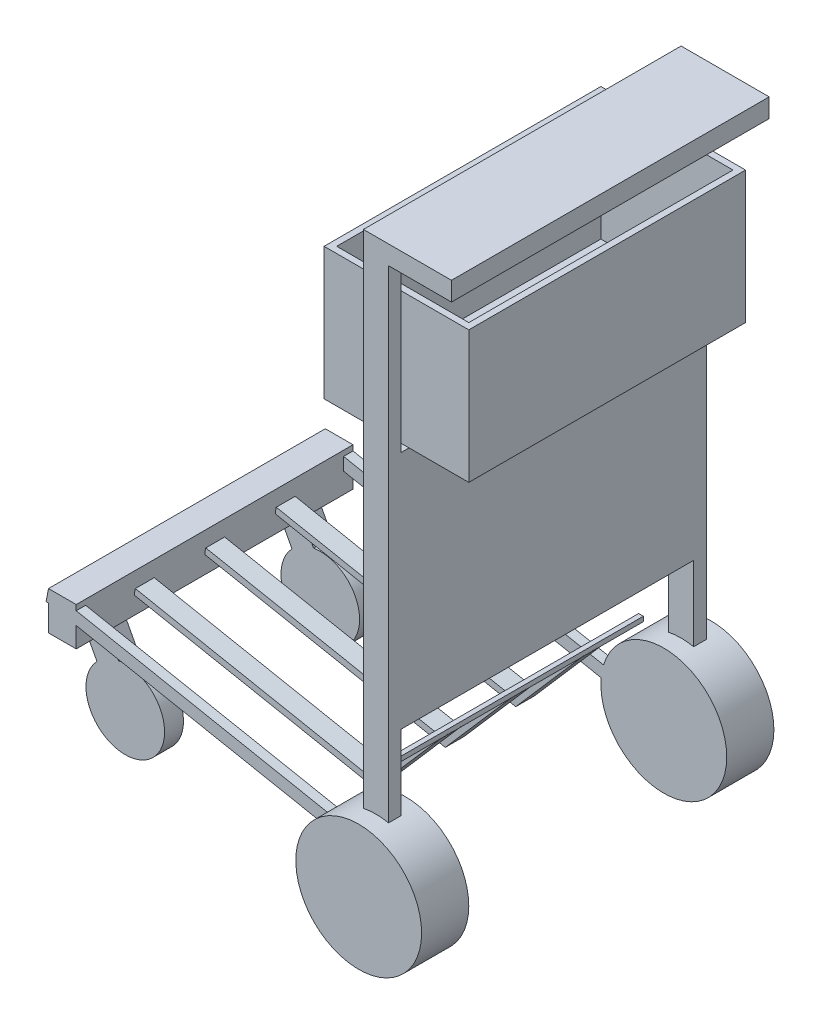
SolidWorks part; units mm, degrees
ref_plane "Front Plane" through (0, 0, 0) normal (0, 0, 1) x (1, 0, 0)
ref_plane "Top Plane" through (0, 0, 0) normal (0, 1, 0) x (1, 0, 0)
ref_plane "Right Plane" through (0, 0, 0) normal (1, 0, 0) x (0, 0, -1)
sketch "Sketch1" plane through (0, 0, 0) normal (1, 0, 0) x (0, 0, -1)
  line L0 (0, 0) -> (0, 459.3185) construction
  line L10 (-232.5, 0) -> (-252.5, 0)
  line L11 (-232.5, 0) -> (-232.5, 965)
  line L13 (-252.5, 0) -> (-252.5, 995)
  line L14 (252.5, 0) -> (252.5, 995)
  line L15 (232.5, 0) -> (252.5, 0)
  line L16 (232.5, 0) -> (232.5, 965)
  line L18 (-252.5, 995) -> (252.5, 995)
  line L20 (-232.5, 965) -> (232.5, 965)
  dimension "D2" = 465
  dimension "D3" = 995
  dimension "D4" = 30
  dimension "D5" = 20
extrude "Boss-Extrude1" add sketch "Sketch1" along normal blind 40
sketch "Sketch3" plane through (40, 0, 0) normal (1, 0, 0) x (0, 0, -1)
  line L0 (252.5, 0) -> (252.5, 995) construction
  line L1 (-252.5, 995) -> (252.5, 995)
  line L2 (-252.5, 995) -> (-252.5, 965)
  line L3 (-252.5, 965) -> (252.5, 965)
  line L4 (252.5, 995) -> (252.5, 965)
  line L5 (-232.5, 965) -> (232.5, 965) construction
extrude "Boss-Extrude2" add sketch "Sketch3" along normal blind 100
sketch "Sketch5" plane through (0, 0, 0) normal (0, 0, 1) x (1, 0, 0)
  line L1 (40, 0) -> (0, 0) construction
  circle A0 centre (20, 100) radius 100
  point P0 (20, 0)
  dimension "D1" = 200
extrude "Boss-Extrude3" add sketch "Sketch5" along normal blind 75 from offset 205 separate body
extrude "Boss-Extrude4" add sketch "Sketch5<2>" against normal blind 75 from offset 205 offset against normal yes
sketch "Sketch5<2>" plane through (0, 0, 0) normal (0, 0, 1) x (1, 0, 0) same geometry as "Sketch5"
sketch "Sketch7" plane through (40, 0, 0) normal (1, 0, 0) x (0, 0, -1)
  line L0 (-252.5, 965) -> (-252.5, 0) construction
  line L1 (-252.5, 317) -> (252.5, 317)
  line L2 (-252.5, 317) -> (-252.5, 698)
  line L3 (-252.5, 698) -> (252.5, 698)
  line L4 (252.5, 317) -> (252.5, 698)
  line L5 (252.5, 197.9796) -> (252.5, 965) construction
  dimension "D1" = 317
  dimension "D2" = 381
extrude "Boss-Extrude5" add sketch "Sketch7" against normal blind 30
sketch "Sketch8" plane through (0, 698, 0) normal (0, 1, 0) x (1, 0, 0)
  line L0 (0, 0) -> (40, 0) construction
  line L1 (40, 232.5) -> (40, -232.5) construction
  line L3 (-85, -210) -> (125, -210)
  line L4 (-85, -210) -> (-85, 210)
  line L5 (-85, 210) -> (125, 210)
  line L6 (125, -210) -> (125, 210)
  line L7 (-85, -210) -> (125, 210) construction
  line L8 (-85, 210) -> (125, -210) construction
  point P5 (20, 0)
  point P6 (20, 0)
  dimension "D1" = 420
  dimension "D2" = 210
extrude "Extrude-Thin1" add sketch "Sketch8" along normal blind 210 thin thin type one direction wall 10
sketch "Sketch9" plane through (0, 698, 0) normal (0, -1, 0) x (1, 0, 0)
  line L1 (-95, 220) -> (135, 220)
  line L2 (-95, 220) -> (-95, -220)
  line L3 (-95, -220) -> (135, -220)
  line L4 (135, 220) -> (135, -220)
extrude "Boss-Extrude6" add sketch "Sketch9" against normal blind 10
sketch "Sketch10" plane through (0, 0, 0) normal (-1, 0, 0) x (0, 0, 1)
  line L0 (-252.5, 197.9796) -> (-252.5, 995) construction
  line L1 (-252.5, 232.5) -> (252.5, 232.5)
  line L2 (-252.5, 232.5) -> (-252.5, 240)
  line L3 (-252.5, 240) -> (252.5, 240)
  line L4 (252.5, 232.5) -> (252.5, 240)
  line L5 (252.5, 995) -> (252.5, 0) construction
  dimension "D1" = 7.5
  dimension "D2" = 240
extrude "Boss-Extrude7" add sketch "Sketch10" along normal blind 7.5
sketch "Sketch11" plane through (0, 0, 0) normal (0, 0, 1) x (1, 0, 0)
  line L0 (20, 100) -> (-535, 208) construction
  line L1 (21.9101, 109.8159) -> (-533.0899, 217.8159)
  line L2 (18.0899, 90.1841) -> (-536.9101, 198.1841)
  line L3 (21.9101, 109.8159) -> (18.0899, 90.1841)
  line L5 (-533.0899, 217.8159) -> (-536.9101, 198.1841)
  circle A0 centre (20, 100) radius 100 construction
  circle A1 centre (20, 100) radius 100 construction
  point P2 (120, 100)
  dimension "D1" = 208
  dimension "D2" = 655
  dimension "D3" = 555
  dimension "D4" = 10
  dimension "D5" = 10
extrude "Boss-Extrude8" add sketch "Sketch11" along normal blind 15 from offset 205
extrude "Boss-Extrude9" add sketch "Sketch11<2>" against normal blind 15 from offset 205 offset against normal yes
sketch "Sketch11<2>" plane through (0, 0, 0) normal (0, 0, 1) x (1, 0, 0) same geometry as "Sketch11"
sketch "Sketch12" plane through (0, 0, 220) normal (0, 0, 1) x (1, 0, 0)
  line L1 (-533.0899, 217.8159) -> (-489.0422, 217.8159)
  line L2 (-533.0899, 217.8159) -> (-533.0899, 156.6633)
  line L3 (-533.0899, 156.6633) -> (-489.0422, 156.6633)
  line L4 (-489.0422, 217.8159) -> (-489.0422, 156.6633)
extrude "Boss-Extrude10" add sketch "Sketch12" against normal up to surface (440 mm away) up to face at (-306.4564, 163.5266, -220)
sketch "Sketch13" plane through (0, 0, 0) normal (0, 0, 1) x (1, 0, 0)
  line L1 (-533.0899, 156.6633) -> (-489.0422, 156.6633) construction
  line L2 (-511.066, 156.6633) -> (-461.066, 62.5) construction
  line L3 (-493.8861, 165.7857) -> (-443.8861, 71.6224)
  line L4 (-528.246, 147.5409) -> (-478.246, 53.3776)
  circle A0 centre (-461.066, 62.5) radius 62.5
  arc A1 (-493.8861, 165.7857) -> (-528.246, 147.5409) centre (-511.066, 156.6633) ccw
  arc A2 (-478.246, 53.3776) -> (-443.8861, 71.6224) centre (-461.066, 62.5) ccw
  point P2 (-461.066, 0)
  point P5 (-486.066, 109.5817)
  point P6 (-511.066, 156.6633)
  dimension "D1" = 125
  dimension "D2" = 50
extrude "Boss-Extrude11" add sketch "Sketch13" along normal blind 30 from offset 140 contours L3 A1 L4 A0 | L4 A2 L3 A0 | A2 L4 A0 L3 region at (-504.1336, 143.6078, 0) region at (-421.961, 108.9672, 0) region at (-471.8441, 82.7979, 0)
extrude "Boss-Extrude12" add sketch "Sketch13<4>" against normal blind 30 from offset 140 contours A2 L4 A0 L3 | L4 A2 L3 A0 | L3 A1 L4 A0 region at (-504.1336, 143.6078, 0) region at (-421.961, 108.9672, 0) region at (-471.8441, 82.7979, 0) offset against normal yes
sketch "Sketch13<4>" plane through (0, 0, 0) normal (0, 0, 1) x (1, 0, 0) same geometry as "Sketch13"
sketch "Sketch14" plane through (0, 0, 0) normal (0, 0, 1) x (1, 0, 0)
  line L0 (-3.75, 236.25) -> (-109.2299, 114.9599)
  line L1 (-109.2299, 114.9599) -> (-489.0422, 188.8693)
  line L2 (-489.0422, 188.8693) -> (-79.5769, 109.1895) construction
  line L3 (-3.75, 232.5) -> (-3.75, 240) construction
  line L4 (-7.5, 232.5) -> (0, 232.5) construction
  line L5 (-7.5, 240) -> (0, 240) construction
  point P14 (-3.75, 236.25)
  dimension "D1" = 120
extrude "Extrude-Thin5" add sketch "Sketch14" along normal mid plane 30 thin thin type mid plane wall 10
pattern_linear "LPattern1" count 2 spacing 112 along (0, 0, -1) of "Extrude-Thin5"
sketch "Sketch15" plane through (0, 0, -252.5) normal (0, 0, -1) x (-1, 0, 0)
  line L1 (7.5, 240) -> (0, 240)
  line L2 (7.5, 240) -> (7.5, 232.5)
  line L3 (7.5, 232.5) -> (0, 232.5)
  line L4 (0, 240) -> (0, 232.5)
extrude "Cut-Extrude1" cut sketch "Sketch15" against normal blind 60
mirror "Mirror1" about plane through (0, 0, 0) normal (0, 0, 1) of "Cut-Extrude1", "LPattern1"
